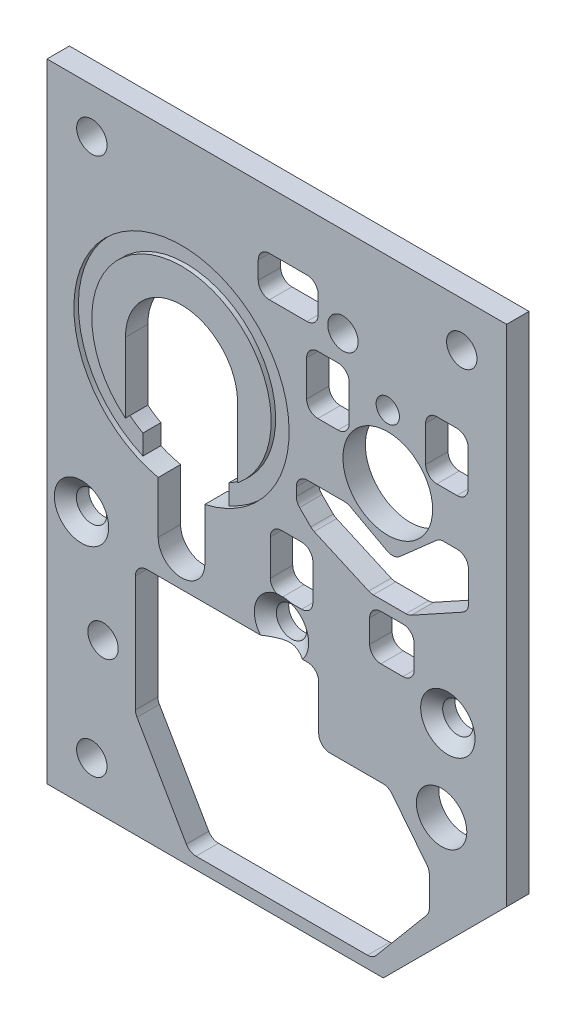
SolidWorks part; units mm, degrees
material "Acrylic (Medium-high impact)"
ref_plane "Front Plane" through (0, 0, 0) normal (0, 0, 1) x (1, 0, 0)
ref_plane "Top Plane" through (0, 0, 0) normal (0, 1, 0) x (1, 0, 0)
ref_plane "Right Plane" through (0, 0, 0) normal (1, 0, 0) x (0, 0, -1)
sketch "Sketch1" plane through (0, 0, 0) normal (0, 0, 1) x (1, 0, 0)
  line L5 (-65.0875, 0) -> (-65.0875, -88.9)
  line L6 (-65.0875, -88.9) -> (-17.4625, -88.9)
  line L7 (-17.4625, -88.9) -> (0, -71.4375)
  line L8 (0, -71.4375) -> (0, 0)
  line L9 (0, 0) -> (-65.0875, 0)
  line L10 (-65.0875, 0) -> (-65.0875, -88.9)
  line L11 (-65.0875, -88.9) -> (-17.4625, -88.9)
  line L12 (-17.4625, -88.9) -> (0, -71.4375)
  line L13 (0, -71.4375) -> (0, 0)
  line L14 (0, 0) -> (-65.0875, 0)
  dimension "D1" = 0
extrude "Boss-Extrude1" add sketch "Sketch1" against normal blind 3.175
hole_wizard "#6 Clearance Hole1" positions "Sketch3" profile "Sketch2" hole size "#6" standard "ANSI Inch" end condition through all
sketch "Sketch3" plane through (0, 0, 0) normal (0, 0, 1) x (1, 0, 0)
  point P0 (-58.7375, -6.35)
  point P3 (-6.35, -6.35)
  point P6 (-23.1775, -12.7)
  point P9 (-57.15, -67.31)
  point P12 (-58.7375, -82.55)
sketch "Sketch2" plane through (-58.7375, -6.35, 0) normal (1, 0, 0) x (0, -1, 0)
  line L0 (0, 0) -> (0, 3.175)
  line L1 (0, 3.175) -> (2.1526, 3.175)
  line L2 (2.1526, 3.175) -> (2.1526, 0)
  line L5 (2.1526, 0) -> (0, 0)
  line L11 (0, -6.35) -> (0, 107.95) construction
  dimension "Thru Hole Dia." = 4.3053
  dimension "Thru Hole Depth" = 3.175
sketch "Sketch4" plane through (0, 0, 0) normal (0, 0, 1) x (1, 0, 0)
  line L0 (-49.3395, -50.8) -> (-49.3395, -43.453) construction
  line L1 (-42.7355, -43.453) -> (-42.7355, -50.8) construction
  line L2 (-49.3395, -50.8) -> (-49.3395, -43.453)
  line L3 (-42.7355, -43.453) -> (-42.7355, -50.8)
  arc A0 (-42.7355, -43.453) -> (-49.3395, -43.453) centre (-46.0375, -28.575) ccw construction
  arc A1 (-49.3395, -50.8) -> (-42.7355, -50.8) centre (-46.0375, -50.8) ccw construction
  arc A2 (-42.7355, -43.453) -> (-49.3395, -43.453) centre (-46.0375, -28.575) ccw
  arc A3 (-49.3395, -50.8) -> (-42.7355, -50.8) centre (-46.0375, -50.8) ccw
extrude "Cut-Extrude1" cut sketch "Sketch4" against normal through all
sketch "Sketch5" plane through (0, 0, 0) normal (0, 0, 1) x (1, 0, 0)
  circle A0 centre (-16.8275, -27.94) radius 6.35
  circle A1 centre (-16.8275, -18.9484) radius 1.651
  dimension "D1" = 12.7
  dimension "D2" = 3.302
  dimension "D3" = 8.9916
extrude "Cut-Extrude2" cut sketch "Sketch5" against normal through all
hole_wizard "1/4 Clearance Hole1" positions "Sketch7" profile "Sketch6" hole size "1/4" standard "ANSI Inch" end condition through all
sketch "Sketch7" plane through (0, 0, 0) normal (0, 0, 1) x (1, 0, 0)
  point P0 (-9.2075, -65.0875)
sketch "Sketch6" plane through (-9.2075, -65.0875, 0) normal (1, 0, 0) x (0, -1, 0)
  line L0 (0, 0) -> (0, 3.175)
  line L1 (0, 3.175) -> (3.5712, 3.175)
  line L2 (3.5712, 3.175) -> (3.5712, 0)
  line L5 (3.5712, 0) -> (0, 0)
  line L11 (0, -6.35) -> (0, 107.95) construction
  dimension "Thru Hole Dia." = 7.1425
  dimension "Thru Hole Depth" = 3.175
sketch "Sketch8" plane through (0, 0, -3.175) normal (0, 0, -1) x (-1, 0, 0)
  line L0 (52.1335, -39.7163) -> (52.1335, -42.5427) construction
  line L1 (53.975, -28.575) -> (53.975, -38.4889) construction
  line L2 (38.1, -38.4889) -> (38.1, -28.575) construction
  line L3 (39.9415, -42.5427) -> (39.9415, -39.7163) construction
  line L4 (52.1335, -39.7163) -> (52.1335, -42.5427)
  line L5 (53.975, -28.575) -> (53.975, -38.4889)
  line L6 (38.1, -38.4889) -> (38.1, -28.575)
  line L7 (39.9415, -42.5427) -> (39.9415, -39.7163)
  arc A0 (52.1335, -39.7163) -> (53.975, -38.4889) centre (46.0375, -28.575) ccw construction
  arc A1 (53.975, -28.575) -> (38.1, -28.575) centre (46.0375, -28.575) ccw construction
  arc A2 (38.1, -38.4889) -> (39.9415, -39.7163) centre (46.0375, -28.575) ccw construction
  arc A3 (49.3395, -43.453) -> (42.7355, -43.453) centre (46.0375, -28.575) ccw construction
  arc A4 (52.1335, -39.7163) -> (53.975, -38.4889) centre (46.0375, -28.575) ccw
  arc A5 (53.975, -28.575) -> (38.1, -28.575) centre (46.0375, -28.575) ccw
  arc A6 (38.1, -38.4889) -> (39.9415, -39.7163) centre (46.0375, -28.575) ccw
  arc A7 (52.1335, -42.5427) -> (39.9415, -42.5427) centre (46.0375, -28.575) ccw
extrude "Boss-Extrude2" add sketch "Sketch8" against normal through all
sketch "Sketch9" plane through (0, 0, 0) normal (0, 0, 1) x (1, 0, 0)
  line L0 (-52.1335, -39.7163) -> (-52.1335, -42.5427) construction
  line L1 (-39.9415, -42.5427) -> (-39.9415, -39.7163) construction
  line L2 (-52.1335, -39.7163) -> (-52.1335, -42.5427)
  line L3 (-39.9415, -42.5427) -> (-39.9415, -39.7163)
  arc A0 (-42.7355, -43.453) -> (-49.3395, -43.453) centre (-46.0375, -28.575) ccw construction
  arc A1 (-53.975, -38.4889) -> (-52.1335, -39.7163) centre (-46.0375, -28.575) ccw construction
  arc A2 (-38.1, -38.4889) -> (-53.975, -38.4889) centre (-46.0375, -28.575) ccw construction
  arc A3 (-39.9415, -39.7163) -> (-38.1, -38.4889) centre (-46.0375, -28.575) ccw construction
  arc A4 (-39.9415, -42.5427) -> (-52.1335, -42.5427) centre (-46.0375, -28.575) ccw
  arc A5 (-53.975, -38.4889) -> (-52.1335, -39.7163) centre (-46.0375, -28.575) ccw
  arc A6 (-38.1, -38.4889) -> (-53.975, -38.4889) centre (-46.0375, -28.575) ccw
  arc A7 (-39.9415, -39.7163) -> (-38.1, -38.4889) centre (-46.0375, -28.575) ccw
extrude "Cut-Extrude3" cut sketch "Sketch9" against normal blind 0.635
hole_wizard "CSK for #6 Flat Head Machine Screw (100)1" positions "Sketch11" profile "Sketch10" countersink size "#6" standard "ANSI Inch" end condition through all
sketch "Sketch11" plane through (0, 0, 0) normal (0, 0, 1) x (1, 0, 0)
  point P1 (-31.877, -53.0919)
  point P5 (-60.198, -53.0919)
  point P8 (-8.321, -53.0919)
sketch "Sketch10" plane through (-31.877, -53.0919, 0) normal (1, 0, 0) x (0, -1, 0)
  line L0 (0, 0) -> (0, 3.175)
  line L1 (0, 3.175) -> (2.1526, 3.175)
  line L2 (2.1526, 3.175) -> (2.1526, 1.4209)
  line L3 (2.1526, 1.4209) -> (3.846, 0)
  line L5 (3.846, 0) -> (0, 0)
  line L6 (-2.1526, 1.4209) -> (-3.846, 0) construction
  line L11 (0, -6.35) -> (0, 107.95) construction
  dimension "Thru Hole Dia." = 4.3053
  dimension "Thru Hole Depth" = 3.175
  dimension "Near C'Sink Dia." = 7.692
  dimension "Near C'Sink Angle" = 100
sketch "Sketch13" plane through (0, 0, 0) normal (0, 0, 1) x (1, 0, 0)
  line L0 (-33.5834, -8.0877) -> (-28.2715, -8.0877)
  line L1 (-26.684, -9.6752) -> (-26.684, -12.1963)
  line L2 (-28.2715, -13.7838) -> (-33.5834, -13.7838)
  line L3 (-35.1709, -9.6752) -> (-35.1709, -12.1963)
  line L4 (-9.8743, -16.2715) -> (-7.0294, -16.2715)
  line L5 (-5.4419, -17.859) -> (-5.4419, -22.9231)
  line L6 (-7.0294, -24.5106) -> (-9.8743, -24.5106)
  line L7 (-11.4618, -22.9231) -> (-11.4618, -17.859)
  line L8 (-26.728, -16.6728) -> (-23.8831, -16.6728)
  line L9 (-22.2956, -18.2603) -> (-22.2956, -23.3243)
  line L10 (-23.8831, -24.9118) -> (-26.728, -24.9118)
  line L11 (-28.3155, -23.3243) -> (-28.3155, -18.2603)
  line L16 (-17.8049, -44.1049) -> (-14.6783, -44.1049)
  line L17 (-13.0908, -45.6924) -> (-13.0908, -48.9531)
  line L18 (-14.6783, -50.5406) -> (-17.8049, -50.5406)
  line L19 (-19.3924, -48.9531) -> (-19.3924, -45.6924)
  line L20 (-31.8736, -41.2169) -> (-29.0288, -41.2169)
  line L21 (-27.4413, -42.8044) -> (-27.4413, -47.8684)
  line L22 (-29.0288, -49.4559) -> (-31.8736, -49.4559)
  line L23 (-33.4611, -47.8684) -> (-33.4611, -42.8044)
  line L24 (-29.3162, -37.1302) -> (-27.7292, -38.7172)
  line L25 (-27.2516, -39.0452) -> (-19.5276, -42.4798)
  line L26 (-18.8826, -42.6167) -> (-14.2496, -42.6167)
  line L27 (-13.4825, -42.4191) -> (-6.223, -38.413)
  line L28 (-5.4025, -37.0231) -> (-5.4025, -32.6722)
  line L29 (-6.99, -31.0847) -> (-8.8978, -31.0847)
  line L30 (-9.9472, -31.481) -> (-15.1221, -36.04)
  line L31 (-16.9251, -36.2461) -> (-22.1779, -33.4131)
  line L32 (-22.9315, -33.2229) -> (-28.1937, -33.2229)
  line L33 (-29.7812, -34.8104) -> (-29.7812, -36.0077)
  line L34 (-50.973, -55.5391) -> (-28.1941, -55.5391)
  line L35 (-26.6066, -57.1266) -> (-26.6066, -63.4989)
  line L36 (-25.0191, -65.0864) -> (-17.4867, -65.0864)
  line L37 (-16.2425, -65.6879) -> (-11.2895, -71.9377)
  line L38 (-10.9462, -72.9237) -> (-10.9462, -77.1078)
  line L39 (-11.3183, -78.129) -> (-18.4811, -86.653)
  line L40 (-19.6965, -87.2192) -> (-43.9811, -87.2192)
  line L41 (-45.3548, -86.4273) -> (-52.3467, -74.3556)
  line L42 (-52.5605, -73.56) -> (-52.5605, -57.1266)
  arc A0 (-28.2715, -8.0877) -> (-26.684, -9.6752) centre (-28.2715, -9.6752) cw
  arc A1 (-26.684, -12.1963) -> (-28.2715, -13.7838) centre (-28.2715, -12.1963) cw
  arc A2 (-33.5834, -13.7838) -> (-35.1709, -12.1963) centre (-33.5834, -12.1963) cw
  arc A3 (-33.5834, -8.0877) -> (-35.1709, -9.6752) centre (-33.5834, -9.6752) ccw
  arc A4 (-5.4419, -22.9231) -> (-7.0294, -24.5106) centre (-7.0294, -22.9231) cw
  arc A5 (-9.8743, -24.5106) -> (-11.4618, -22.9231) centre (-9.8743, -22.9231) cw
  arc A6 (-9.8743, -16.2715) -> (-11.4618, -17.859) centre (-9.8743, -17.859) ccw
  arc A7 (-7.0294, -16.2715) -> (-5.4419, -17.859) centre (-7.0294, -17.859) cw
  arc A8 (-22.2956, -23.3243) -> (-23.8831, -24.9118) centre (-23.8831, -23.3243) cw
  arc A9 (-26.728, -24.9118) -> (-28.3155, -23.3243) centre (-26.728, -23.3243) cw
  arc A10 (-26.728, -16.6728) -> (-28.3155, -18.2603) centre (-26.728, -18.2603) ccw
  arc A11 (-23.8831, -16.6728) -> (-22.2956, -18.2603) centre (-23.8831, -18.2603) cw
  arc A16 (-13.0908, -48.9531) -> (-14.6783, -50.5406) centre (-14.6783, -48.9531) cw
  arc A17 (-17.8049, -50.5406) -> (-19.3924, -48.9531) centre (-17.8049, -48.9531) cw
  arc A18 (-17.8049, -44.1049) -> (-19.3924, -45.6924) centre (-17.8049, -45.6924) ccw
  arc A19 (-14.6783, -44.1049) -> (-13.0908, -45.6924) centre (-14.6783, -45.6924) cw
  arc A20 (-27.4413, -47.8684) -> (-29.0288, -49.4559) centre (-29.0288, -47.8684) cw
  arc A21 (-31.8736, -49.4559) -> (-33.4611, -47.8684) centre (-31.8736, -47.8684) cw
  arc A22 (-31.8736, -41.2169) -> (-33.4611, -42.8044) centre (-31.8736, -42.8044) ccw
  arc A23 (-29.0288, -41.2169) -> (-27.4413, -42.8044) centre (-29.0288, -42.8044) cw
  arc A24 (-19.5276, -42.4798) -> (-18.8826, -42.6167) centre (-18.8826, -41.0292) ccw
  arc A25 (-14.2496, -42.6167) -> (-13.4825, -42.4191) centre (-14.2496, -41.0292) ccw
  arc A26 (-6.223, -38.413) -> (-5.4025, -37.0231) centre (-6.99, -37.0231) ccw
  arc A27 (-5.4025, -32.6722) -> (-6.99, -31.0847) centre (-6.99, -32.6722) ccw
  arc A28 (-8.8978, -31.0847) -> (-9.9472, -31.481) centre (-8.8978, -32.6722) ccw
  arc A29 (-15.1221, -36.04) -> (-16.9251, -36.2461) centre (-16.1715, -34.8488) cw
  arc A30 (-22.1779, -33.4131) -> (-22.9315, -33.2229) centre (-22.9315, -34.8104) ccw
  arc A31 (-27.7292, -38.7172) -> (-27.2516, -39.0452) centre (-26.6066, -37.5947) ccw
  arc A32 (-29.3162, -37.1302) -> (-29.7812, -36.0077) centre (-28.1937, -36.0077) cw
  arc A33 (-28.1937, -33.2229) -> (-29.7812, -34.8104) centre (-28.1937, -34.8104) ccw
  arc A34 (-28.1941, -55.5391) -> (-26.6066, -57.1266) centre (-28.1941, -57.1266) cw
  arc A35 (-26.6066, -63.4989) -> (-25.0191, -65.0864) centre (-25.0191, -63.4989) ccw
  arc A36 (-17.4867, -65.0864) -> (-16.2425, -65.6879) centre (-17.4867, -66.6739) cw
  arc A37 (-11.2895, -71.9377) -> (-10.9462, -72.9237) centre (-12.5337, -72.9237) cw
  arc A38 (-10.9462, -77.1078) -> (-11.3183, -78.129) centre (-12.5337, -77.1078) cw
  arc A39 (-18.4811, -86.653) -> (-19.6965, -87.2192) centre (-19.6965, -85.6317) cw
  arc A40 (-43.9811, -87.2192) -> (-45.3548, -86.4273) centre (-43.9811, -85.6317) cw
  arc A41 (-52.3467, -74.3556) -> (-52.5605, -73.56) centre (-50.973, -73.56) cw
  arc A42 (-50.973, -55.5391) -> (-52.5605, -57.1266) centre (-50.973, -57.1266) ccw
  dimension "D1" = 1.5875
  dimension "D2" = 1.5875
  dimension "D3" = 1.5875
  dimension "D4" = 1.5875
  dimension "D5" = 1.5875
extrude "Cut-Extrude4" cut sketch "Sketch13" against normal through all
